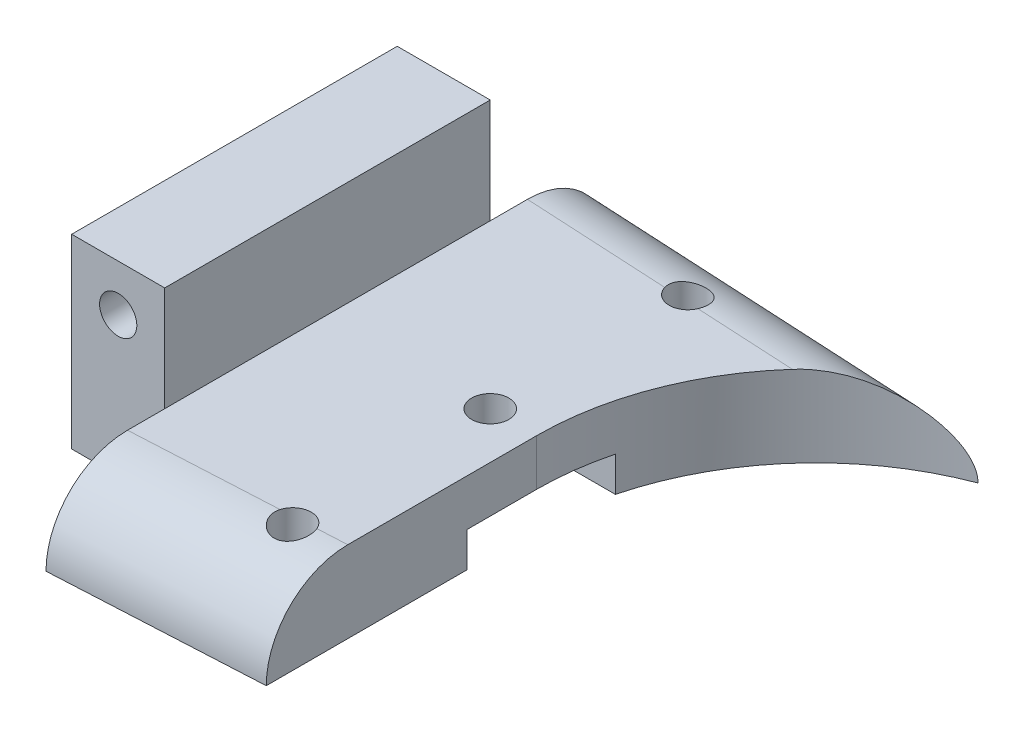
SolidWorks part; units mm, degrees
ref_plane "Front" through (0, 0, 0) normal (0, 0, 1) x (1, 0, 0)
ref_plane "Top" through (0, 0, 0) normal (0, 1, 0) x (1, 0, 0)
ref_plane "Right" through (0, 0, 0) normal (1, 0, 0) x (0, 0, -1)
sketch "Sketch1" plane through (0, 0, 0) normal (0, 1, 0) x (1, 0, 0)
  line L0 (0, 0) -> (38, 0) construction
  line L2 (0, 13) -> (17, 12.1053) construction
  line L3 (17, -12.1053) -> (33.7535, -11.2235)
  line L4 (0, -13) -> (17, -12.1053) construction
  line L5 (13, 0) -> (13, 7)
  line L7 (26, 0) -> (26, -11.6316)
  line L8 (17, 10) -> (17, 12.1053)
  line L9 (17, 12.1053) -> (33.7535, 11.2235)
  line L10 (17, -10) -> (17, -12.1053)
  line L13 (13, 7) -> (17, 7)
  line L14 (17, 7) -> (17, 10)
  line L15 (13, 0) -> (13, -7)
  line L16 (13, -7) -> (17, -7)
  line L17 (17, -7) -> (17, -10)
  circle A0 centre (0, 0) radius 13
  circle A1 centre (38, 0) radius 12
extrude "Boss-Extrude1" add sketch "Sketch1" along normal blind 3.5 contours A1 L9 L8 L14 L13 L5 L15 L16 L17 L10 L3 L7 region at (20.8147, 0, -0.7569)
sketch "Sketch2" plane through (0, 0, 0) normal (0, 1, 0) x (1, 0, 0)
  line L0 (0, 0) -> (24, 0) construction
  line L4 (24, 0) -> (24, 8.5) construction
  line L5 (24, 0) -> (24, -8.5) construction
  circle A0 centre (24, 8.5) radius 0.8
  circle A1 centre (24, 0) radius 0.8
  circle A3 centre (24, -8.5) radius 0.8
extrude "Screw Holes" cut sketch "Sketch2" along normal through all
sketch "Sketch3" plane through (0, 0, 0) normal (0, 1, 0) x (1, 0, 0)
  line L1 (13, 7) -> (17, 7)
  line L2 (13, 7) -> (13, -7)
  line L3 (13, -7) -> (17, -7)
  line L4 (17, 7) -> (17, -7)
extrude "Boss-Extrude2" add sketch "Sketch3" along normal blind 8
sketch "Sketch4" plane through (0, 0, 0) normal (0, 1, 0) x (1, 0, 0)
  line L2 (13, 0) -> (13, 3)
  line L5 (13, 0) -> (13, -3)
  line L6 (13, -3) -> (26.381, -3)
  line L7 (26.381, -3) -> (26.381, 3)
  line L8 (26.381, 3) -> (13, 3)
extrude "Wire Canal" cut sketch "Sketch4" along normal blind 1.5
sketch "Sketch5" plane through (0, 0, 0) normal (0, 0, 1) x (1, 0, 0)
  line L2 (15, -4) -> (15, 6) construction
  circle A0 centre (15, 6) radius 0.8
extrude "Cut-Extrude2" cut sketch "Sketch5" against normal through all from offset 13
fillet "Fillet1" radius 3.5 2 edges at (21.5, 3.5, 11.8684) (25.3767, 3.5, -11.6644)
